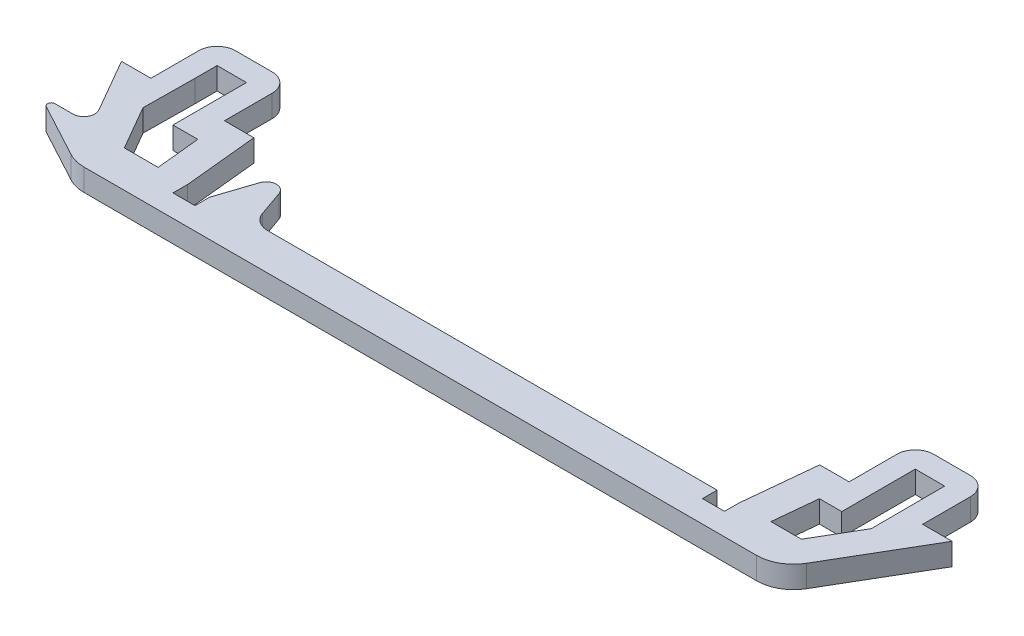
SolidWorks part; units mm, degrees
material "Custom Plastic"
ref_plane "Front Plane" through (0, 0, 0) normal (0, 0, 1) x (1, 0, 0)
ref_plane "Top Plane" through (0, 0, 0) normal (0, 1, 0) x (1, 0, 0)
ref_plane "Right Plane" through (0, 0, 0) normal (1, 0, 0) x (0, 0, -1)
sketch "Sketch1" plane through (0, 0, 0) normal (0, 1, 0) x (1, 0, 0)
  line L0 (-62.4186, -47.1587) -> (-58.4186, -47.1587)
  line L1 (-58.4186, -47.1587) -> (-58.4186, -38.1587)
  line L2 (-58.4186, -38.1587) -> (-48.4186, -38.1587)
  line L3 (-48.4186, -38.1587) -> (-48.4186, -47.1587)
  line L4 (-48.4186, -47.1587) -> (-44.4186, -47.1587)
  line L5 (-44.4186, -47.1587) -> (-43.4188, -57.1562)
  line L7 (31.5814, -57.2088) -> (32.5814, -47.2113)
  line L8 (32.5814, -47.2113) -> (36.5814, -47.2113)
  line L9 (36.5814, -47.2113) -> (36.5814, -38.2113)
  line L10 (36.5814, -38.2113) -> (46.5814, -38.2113)
  line L11 (46.5814, -38.2113) -> (46.5814, -47.2113)
  line L12 (46.5814, -47.2113) -> (50.5814, -47.2113)
  line L13 (50.5814, -47.2113) -> (41.8306, -62.1587)
  line L14 (41.8306, -62.1587) -> (-53.7583, -62.1587)
  line L15 (-58.2259, -54.4205) -> (-62.4186, -47.1587)
  line L16 (36.5478, -51.2113) -> (39.5814, -51.2113)
  line L17 (-55.4186, -41.1587) -> (-51.4186, -41.1587)
  line L18 (-55.4186, -41.1587) -> (-55.4186, -44.1587)
  line L20 (-51.4186, -41.1587) -> (-51.4186, -44.1587)
  line L21 (39.5814, -41.2113) -> (43.5814, -41.2113)
  line L22 (39.5814, -41.2113) -> (39.5814, -44.2113)
  line L24 (43.5814, -41.2113) -> (43.5814, -44.2113)
  line L25 (43.6046, -51.2113) -> (40.0934, -57.2088)
  line L26 (40.0934, -57.2088) -> (35.9479, -57.2088)
  line L27 (35.9479, -57.2088) -> (36.5478, -51.2113)
  line L28 (-51.4186, -51.1587) -> (-48.0385, -51.1587)
  line L29 (-48.0385, -51.1587) -> (-47.4385, -57.1587)
  line L30 (-47.4385, -57.1587) -> (-52.0263, -57.1587)
  line L31 (-52.0263, -57.1587) -> (-55.4904, -51.1587)
  line L32 (28.5814, -57.1587) -> (28.5814, -59.1587)
  line L33 (28.5814, -47.1587) -> (28.5814, -62.1587) construction
  line L34 (28.5814, -59.1587) -> (31.5814, -59.1587)
  line L35 (31.5814, -59.1587) -> (31.5814, -57.2088)
  line L36 (31.5814, -62.1587) -> (31.5814, -47.1587) construction
  line L38 (-43.4188, -57.1562) -> (-43.4188, -59.1587)
  line L39 (-43.4188, -59.1587) -> (-40.4188, -59.1587)
  line L40 (-40.4188, -59.1587) -> (-40.4188, -57.1587)
  line L41 (-34.3352, -57.1587) -> (28.5814, -57.1587)
  line L42 (-34.3352, -57.1587) -> (-36.1291, -52.0241)
  line L43 (43.5814, -44.2113) -> (43.6046, -51.2113)
  line L44 (-38.7227, -52.0447) -> (-40.4188, -57.1587)
  line L45 (39.5814, -44.2113) -> (39.5814, -51.2113)
  line L46 (-55.4186, -44.1587) -> (-55.4904, -51.1587)
  line L47 (-51.4186, -44.1587) -> (-51.4186, -51.1587)
  line L48 (-53.7583, -62.1587) -> (-62.2024, -57.6107)
  line L49 (-61.9653, -56.6705) -> (-59.525, -56.6705)
  arc A0 (-38.7227, -52.0447) -> (-36.1291, -52.0241) centre (-37.4224, -52.4759) cw
  arc A1 (-59.525, -56.6705) -> (-58.2259, -54.4205) centre (-59.525, -55.1705) ccw
  arc A2 (-62.2024, -57.6107) -> (-61.9653, -56.6705) centre (-61.9653, -57.1705) cw
  dimension "D6" = 0.5
  dimension "D5" = 1.5
  dimension "D1" = 15
  dimension "D2" = 4
  dimension "D3" = 9
  dimension "D4" = 3
  dimension "D7" = 120
  dimension "D8" = 10
  dimension "D9" = 85
  dimension "D10" = 3
  dimension "D11" = 95.5889
  dimension "D12" = 3
  dimension "D13" = 3
  dimension "D14" = 3
  dimension "D15" = 3
  dimension "D17" = 4
  dimension "D18" = 4
  dimension "D19" = 4
  dimension "D20" = 4
  dimension "D21" = 4
  dimension "D23" = 2
  dimension "D24" = 3
extrude "Boss-Extrude1" add sketch "Sketch1" along normal blind 3
fillet "Fillet1" radius 5 2 edges at (41.8306, 1.5, 62.1587) (-53.7583, 1.5, 62.1587)
fillet "Fillet2" radius 2.5 4 edges at (46.5814, 1.5, 38.2113) (36.5814, 1.5, 38.2113) (-58.4186, 1.5, 38.1587) (-48.4186, 1.5, 38.1587)
fillet "Fillet3" radius 2.5 1 edges at (-34.3352, 1.5, 57.1587)
